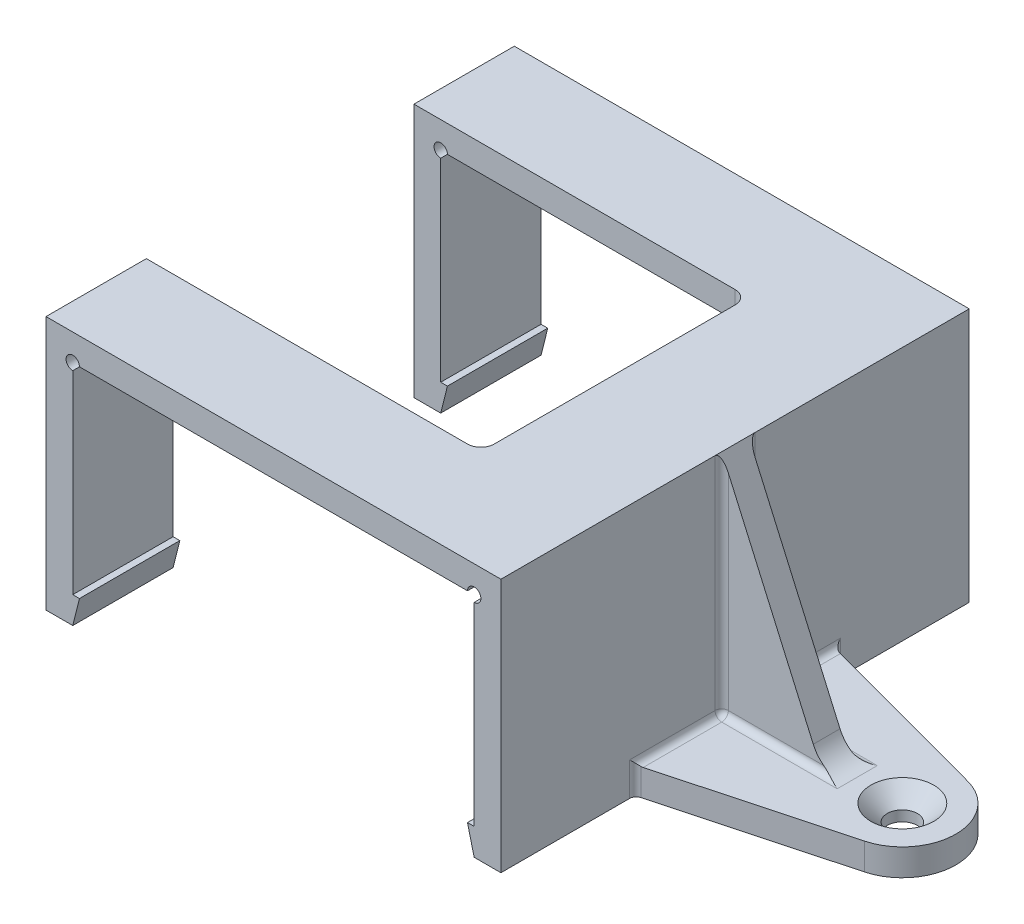
SolidWorks part; units mm, degrees
ref_plane "Plan de face" through (0, 0, 0) normal (0, 0, 1) x (1, 0, 0)
ref_plane "Plan de dessus" through (0, 0, 0) normal (0, 1, 0) x (1, 0, 0)
ref_plane "Plan de droite" through (0, 0, 0) normal (1, 0, 0) x (0, 0, -1)
sketch "Esquisse1" plane through (0, 0, 0) normal (0, 0, 1) x (1, 0, 0)
  line L0 (0, -38) -> (0, 0)
  line L1 (0, 0) -> (68, 0)
  line L2 (68, 0) -> (68, -38)
  line L3 (68, -38) -> (64, -38)
  line L4 (64, -38) -> (63, -34)
  line L5 (63, -34) -> (64, -34)
  line L6 (64, -34) -> (64, -4)
  line L7 (64, -4) -> (4, -4)
  line L8 (4, -4) -> (4, -34)
  line L9 (4, -34) -> (5, -34)
  line L10 (5, -34) -> (4, -38)
  line L11 (4, -38) -> (0, -38)
  dimension "D2" = 4
  dimension "D3" = 4
  dimension "D4" = 4
  dimension "D5" = 4
  dimension "D6" = 4
  dimension "D7" = 1
  dimension "D8" = 4
  dimension "D9" = 1
  dimension "D10" = 4
extrude "Forme principale" add sketch "Esquisse1" along normal mid plane 70
sketch "Esquisse3" plane through (0, 0, 0) normal (0, 1, 0) x (1, 0, 0)
  line L0 (50, 20) -> (0, 20)
  line L1 (50, 20) -> (50, -20)
  line L2 (0, 20) -> (0, -20)
  line L3 (50, -20) -> (0, -20)
  line L4 (50, 20) -> (0, -20) construction
  line L5 (0, 20) -> (50, -20) construction
  line L6 (0, -35) -> (0, 35) construction
  point P1 (25, 0)
  dimension "D1" = 40
  dimension "D2" = 50
extrude "Évidement" cut sketch "Esquisse3" against normal through all
sketch "Esquisse4" plane through (0, -38, 0) normal (0, -1, 0) x (1, 0, 0)
  line L0 (68, 15) -> (95.0756, 7.726)
  line L1 (68, 35) -> (68, -35) construction
  line L2 (95.0756, -7.726) -> (68, -15)
  line L3 (68, -15) -> (68, 15)
  arc A0 (95.0756, 7.726) -> (95.0756, -7.726) centre (93, 0) cw
  point P6 (68, 0)
  dimension "D2" = 8
  dimension "D1" = 25
  dimension "D3" = 30
extrude "Bossage écrou" add sketch "Esquisse4" against normal blind 4
hole_wizard "Fraisage pour vis à tête fraisée M41" positions "Esquisse8" profile "Esquisse7" countersink size "M4" standard "ISO" end condition through all
sketch "Esquisse8" plane through (0, -34, 0) normal (0, 1, 0) x (1, 0, 0)
  point P0 (93, 0)
  point P3 (93, 0)
sketch "Esquisse7" plane through (93, -34, 0) normal (1, 0, 0) x (0, 0, 1)
  line L0 (0, 0) -> (0, 4.0001)
  line L1 (0, 4.0001) -> (2.25, 4.0001)
  line L2 (2.25, 4.0001) -> (2.25, 2.45)
  line L3 (2.25, 2.45) -> (4.7, 0)
  line L5 (4.7, 0) -> (0, 0)
  line L6 (-2.25, 2.45) -> (-4.7, 0) construction
  line L11 (0, -6.35) -> (0, 107.95) construction
  dimension "Diamètre du perçage jusqu'au prochain" = 4.5
  dimension "Profondeur du perçage jusqu'au prochain" = 4.0001
  dimension "Diamètre du fraisage entrant" = 9.4
  dimension "Angle du fraisage entrant" = 90
sketch "Esquisse9" plane through (0, 0, 0) normal (0, 0, 1) x (1, 0, 0)
  line L0 (68, 0) -> (83, -34)
  line L3 (93, -34) -> (93, -38) construction
  dimension "D1" = 10
rib "Nervure3" sketch "Esquisse9" sketch "Esquisse9" thickness 4 extrusion direction parallel to sketch draft on no parameters "D1"=4
fillet "Congé2" radius 1 8 edges at (68, -34, -8.5) (75.5, -34, -2) (68, -17, -2) (75.5, -34, 2) (68, -34, 8.5) (68, -17, 2)
fillet "Congé3" radius 5 1 edges at (83, -34, 0)
fillet "Congé4" radius 2 2 edges at (50, -2, -20) (50, -2, 20)
sketch "Esquisse10" plane through (0, 0, -35) normal (0, 0, -1) x (-1, 0, 0)
  circle A0 centre (-64, -4) radius 1
  circle A1 centre (-4, -4) radius 1
  dimension "D1" = 2
  dimension "D2" = 2
extrude "Enlèv. mat.-Extru.1" cut sketch "Esquisse10" against normal through all
sketch "Esquisse11" plane through (0, -34, 0) normal (0, 1, 0) x (1, 0, 0)
  line L0 (63, -35) -> (63, 35) construction
  line L1 (64, 20) -> (63, 20)
  line L2 (64, 20) -> (64, -20)
  line L3 (64, -20) -> (63, -20)
  line L4 (63, 20) -> (63, -20)
  line L5 (64, -35) -> (64, 35) construction
extrude "Enlèv. mat.-Extru.2" cut sketch "Esquisse11" against normal through all
